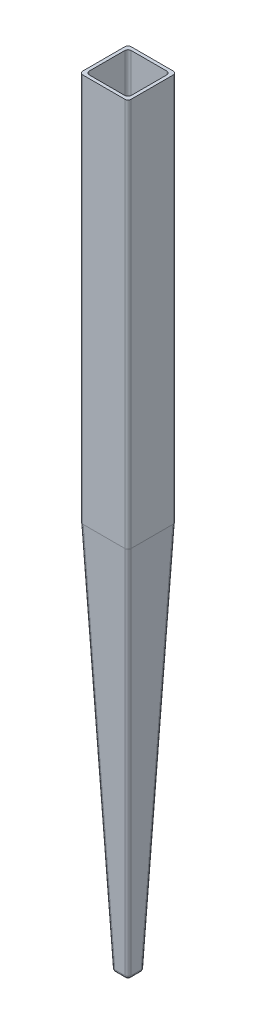
SolidWorks part; units mm, degrees
ref_plane "Front Plane" through (0, 0, 0) normal (0, 0, 1) x (1, 0, 0)
ref_plane "Top Plane" through (0, 0, 0) normal (0, 1, 0) x (1, 0, 0)
ref_plane "Right Plane" through (0, 0, 0) normal (1, 0, 0) x (0, 0, -1)
sketch "Sketch1" plane through (0, 0, 0) normal (0, 1, 0) x (1, 0, 0)
  line L1 (-19.05, -19.05) -> (19.05, -19.05)
  line L2 (-19.05, -19.05) -> (-19.05, 19.05)
  line L3 (-19.05, 19.05) -> (19.05, 19.05)
  line L4 (19.05, -19.05) -> (19.05, 19.05)
  line L5 (-19.05, -19.05) -> (19.05, 19.05) construction
  line L6 (-19.05, 19.05) -> (19.05, -19.05) construction
  point P0 (0, 0)
  dimension "D1" = 38.1
  dimension "D2" = 38.1
extrude "Boss-Extrude1" add sketch "Sketch1" along normal blind 304.8
shell "Shell1" thickness 2.54 removed face at (0, 304.8, 0)
sketch "Sketch2" plane through (0, 0, 0) normal (0, -1, 0) x (1, 0, 0)
  line L1 (-6.35, -6.35) -> (6.35, -6.35)
  line L2 (-6.35, -6.35) -> (-6.35, 6.35)
  line L3 (-6.35, 6.35) -> (6.35, 6.35)
  line L4 (6.35, -6.35) -> (6.35, 6.35)
  line L5 (-6.35, -6.35) -> (6.35, 6.35) construction
  line L6 (-6.35, 6.35) -> (6.35, -6.35) construction
  point P0 (0, 0)
  dimension "D1" = 12.7
  dimension "D2" = 12.7
extrude "Boss-Extrude2" add sketch "Sketch2" along normal blind 304.8
draft "Draft2" type of draft neutral plane draft angle 2.35 faces to draft 4 face at (0, -152.4, -6.35) face at (-6.35, -152.4, 0) face at (0, -152.4, 6.35) face at (6.35, -152.4, 0) neutral plane through (0, -304.8, 0) neutral plane normal (0, -1, 0) parameters "D1"=2.35
shell "Shell2" thickness 2.54
fillet "Fillet1" radius 2.54 8 edges at (-19.05, 152.4, -19.05) (19.05, 152.4, -19.05) (19.05, 152.4, 19.05) (-19.05, 152.4, 19.05) (-12.6042, -152.4, -12.6042) (12.6042, -152.4, -12.6042) (12.6042, -152.4, 12.6042) (-12.6042, -152.4, 12.6042)
fillet "Fillet2" radius 2.54 4 edges at (-16.51, 153.67, -16.51) (16.51, 153.67, -16.51) (-16.51, 153.67, 16.51) (16.51, 153.67, 16.51)
fillet "Fillet3" radius 2.54 8 edges at (5.6069, -304.8, -5.6069) (0, -304.8, -6.35) (-5.6069, -304.8, -5.6069) (-6.35, -304.8, 0) (-5.6069, -304.8, 5.6069) (0, -304.8, 6.35) (5.6069, -304.8, 5.6069) (6.35, -304.8, 0)
